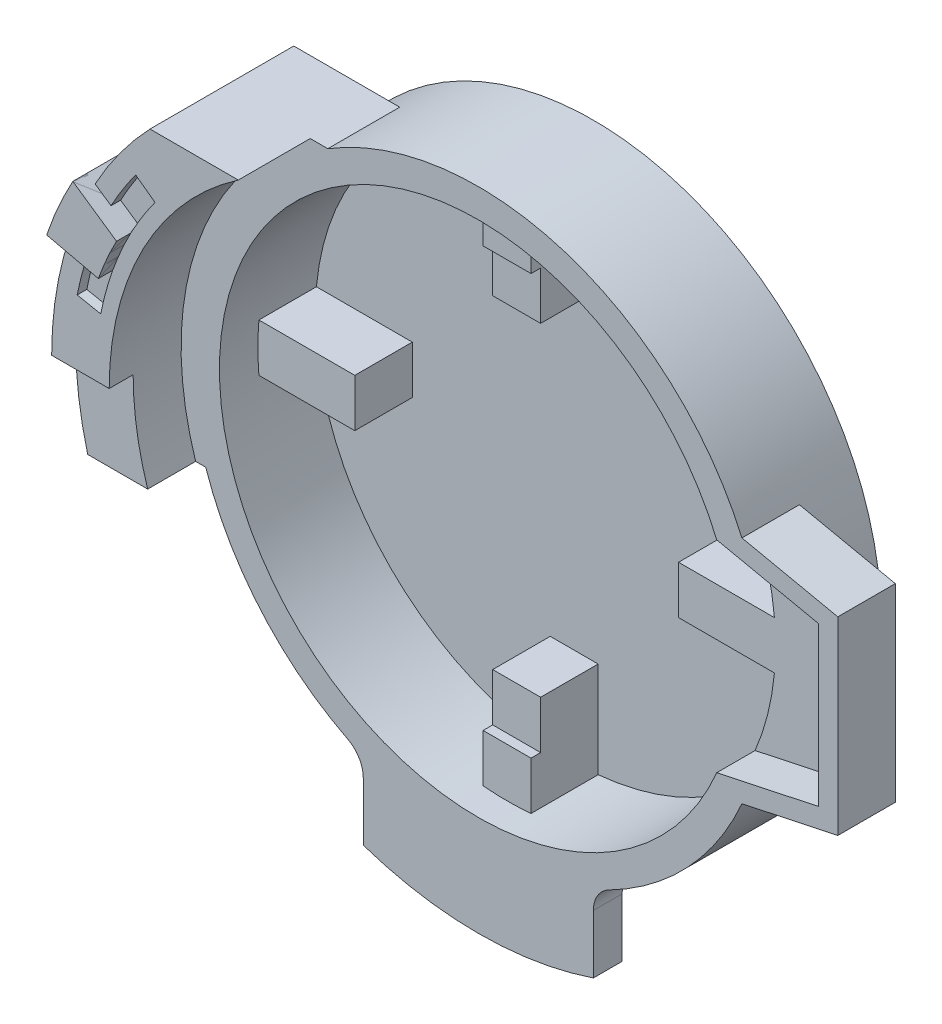
SolidWorks part; units mm, degrees
ref_plane "Front Plane" through (0, 0, 0) normal (0, 0, 1) x (1, 0, 0)
ref_plane "Top Plane" through (0, 0, 0) normal (0, 1, 0) x (1, 0, 0)
ref_plane "Right Plane" through (0, 0, 0) normal (1, 0, 0) x (0, 0, -1)
sketch "草图1" plane through (0, 0, 0) normal (0, 0, 1) x (1, 0, 0)
  circle A0 centre (0, 0) radius 30
  dimension "D1" = 60
extrude "凸台-拉伸1" add sketch "草图1" along normal blind 2
sketch "草图5" plane through (0, 0, 2) normal (0, 0, 1) x (1, 0, 0)
  circle A0 centre (0, 0) radius 30
  circle A1 centre (0, 0) radius 27
  dimension "D1" = 60
  dimension "D2" = 54
extrude "凸台-拉伸2" add sketch "草图5" along normal blind 10 contours A0 | A1
sketch "草图6" plane through (0, 0, 12) normal (0, 0, 1) x (1, 0, 0)
  line L0 (-12, -27.4955) -> (-12, -35.4955)
  line L2 (12, -35.4955) -> (12, -27.4955)
  circle A0 centre (0, 0) radius 30 construction
  arc A1 (-12, -27.4955) -> (12, -27.4955) centre (0, 0) ccw
  arc A2 (-12, -35.4955) -> (12, -35.4955) centre (0, 0) ccw
  dimension "D1" = 8
  dimension "D2" = 24
extrude "凸台-拉伸3" add sketch "草图6" against normal blind 3
fillet "圆角2" radius 3 1 edges at (-12, -27.4955, 10.5)
fillet "圆角3" radius 3 1 edges at (12, -27.4955, 10.5)
sketch "草图8" plane through (0, 0, 12) normal (0, 0, 1) x (1, 0, 0)
  line L0 (27.4945, -12.0022) -> (37.4945, -12.0022)
  line L1 (37.4945, -12.0022) -> (37.4945, 12.0022)
  line L2 (37.4945, 12.0022) -> (27.4945, 12.0022)
  circle A0 centre (0, 0) radius 30 construction
  arc A1 (27.4945, -12.0022) -> (27.4945, 12.0022) centre (0, 0) ccw
extrude "凸台-拉伸4" add sketch "草图8" against normal blind 6
sketch "草图13" plane through (0, 0, 12) normal (0, 0, 1) x (1, 0, 0)
  line L0 (-26.7466, 25.566) -> (-15.6965, 25.566)
  line L1 (-37, 0) -> (-30, 0)
  arc A0 (-26.7466, 25.566) -> (-37, 0) centre (0, 0) ccw
  arc A1 (-15.6965, 25.566) -> (-30, 0) centre (0, 0) ccw
  dimension "D1" = 37
  dimension "D2" = 30
extrude "凸台-拉伸6" add sketch "草图13" against normal mid plane 15
sketch "草图14" plane through (0, 0, 19.5) normal (0, 0, 1) x (1, 0, 0)
  circle A0 centre (0, 0) radius 31
  dimension "D1" = 62
extrude "切除-拉伸3" cut sketch "草图14" against normal up to surface (7.5 mm away) up to face at (6.7958, -12.5812, 12)
chamfer "倒角4" distance 10 angle 12 1 edges at (37.4945, 12.0022, 9) first distance on face at (32.4945, 12.0022, 9)
chamfer "倒角5" distance 10 angle 12 1 edges at (37.4945, -12.0022, 9) first distance on face at (32.4945, -12.0022, 9)
sketch "草图16" plane through (0, 0, 12) normal (0, 0, 1) x (1, 0, 0)
  line L0 (27.838, 9.8845) -> (35.4945, 8.257)
  line L1 (35.4945, 8.257) -> (35.4945, -8.257)
  line L2 (35.4945, -8.257) -> (21.8753, -11.1519)
  line L3 (21.8753, -11.1519) -> (18.3562, 11.8999)
  line L4 (18.3562, 11.8999) -> (27.838, 9.8845)
  line L5 (27.4945, -12.0022) -> (37.4945, -9.8766) construction
  line L6 (37.4945, -9.8766) -> (37.4945, 9.8766) construction
  line L7 (37.4945, 9.8766) -> (27.4945, 12.0022) construction
  line L8 (27.4945, -12.0022) -> (37.4945, -9.8766)
  line L9 (37.4945, -9.8766) -> (37.4945, 9.8766)
  line L10 (37.4945, 9.8766) -> (27.4945, 12.0022)
  circle M23 centre (0, 0) radius 27
  dimension "D1" = 2
  dimension "D2" = 2
  dimension "D3" = 2
extrude "切除-拉伸6" cut sketch "草图16" against normal blind 4 contours L4 L3 L2 M23 | L4 L2 L1 L0 M23 region at (30.7235, 0, 12) region at (23.1122, 1.1598, 12)
sketch "草图17" plane through (0, 0, 12) normal (0, 0, 1) x (1, 0, 0)
  line L0 (-28.4305, -9.5763) -> (-35.7393, -9.5763)
  line L1 (-37, 0) -> (-31, 0) construction
  line L2 (-30, 0) -> (-31, 0) construction
  line L3 (-37, 0) -> (-31, 0)
  line L4 (-30, 0) -> (-31, 0)
  arc A0 (-37, 0) -> (-35.7393, -9.5763) centre (0, 0) ccw
  arc A1 (-30, 0) -> (-28.4305, -9.5763) centre (0, 0) ccw
extrude "凸台-拉伸10" add sketch "草图17" along normal mid plane 10
sketch "草图18" plane through (0, 0, 12) normal (0, 0, 1) x (1, 0, 0)
  line L0 (-35.7393, -9.5763) -> (-28.4305, -9.5763) construction
  line L1 (-30, 0) -> (-31, 0) construction
  line L2 (-35.7393, -9.5763) -> (-28.4305, -9.5763)
  line L3 (-30, 0) -> (-31, 0)
  circle A0 centre (0, 0) radius 31
  circle A1 centre (0, 0) radius 30 construction
  circle A2 centre (0, 0) radius 30
  line M9 (-31, 0) -> (-30, 0)
  arc M10 (-30, 0) -> (-28.4305, -9.5763) centre (0, 0) ccw
extrude "切除-拉伸7" cut sketch "草图18" along normal blind 6 contours A0 L2 M9 M10 region at (-29.984, -4.8293, 12)
sketch "草图19" plane through (0, 0, 2) normal (0, 0, 1) x (1, 0, 0)
  line L0 (-2.5, 26.884) -> (-2.5, 16.884)
  line L1 (-2.5, 16.884) -> (2.5, 16.884)
  line L2 (2.5, 16.884) -> (2.5, 26.884)
  line L3 (26.884, 2.5) -> (16.884, 2.5)
  line L4 (16.884, -2.5) -> (26.884, -2.5)
  line L5 (16.884, 2.5) -> (16.884, -2.5)
  line L6 (2.5, -26.884) -> (2.5, -16.884)
  line L7 (-2.5, -16.884) -> (-2.5, -26.884)
  line L8 (2.5, -16.884) -> (-2.5, -16.884)
  line L9 (-26.884, -2.5) -> (-16.884, -2.5)
  line L10 (-16.884, 2.5) -> (-26.884, 2.5)
  line L11 (-16.884, -2.5) -> (-16.884, 2.5)
  circle A0 centre (0, 0) radius 27 construction
  arc A1 (24.868, 10.5158) -> (24.868, -10.5158) centre (0, 0) ccw construction
  arc A2 (2.5, 26.884) -> (-2.5, 26.884) centre (0, 0) ccw
  arc A3 (26.884, -2.5) -> (26.884, 2.5) centre (0, 0) ccw
  arc A4 (-2.5, -26.884) -> (2.5, -26.884) centre (0, 0) ccw
  arc A5 (-26.884, 2.5) -> (-26.884, -2.5) centre (0, 0) ccw
  point P26 (0, 0)
  dimension "D1" = 4
extrude "凸台-拉伸11" add sketch "草图19" along normal blind 6
sketch "草图20" plane through (0, 0, 8) normal (0, 0, 1) x (1, 0, 0)
  line L0 (-2.5, 26.884) -> (-2.5, 21.884)
  line L1 (-2.5, 21.884) -> (2.5, 21.884)
  line L2 (2.5, 21.884) -> (2.5, 26.884)
  line L9 (-2.5, 26.884) -> (-2.5, 16.884)
  line L10 (-2.5, 16.884) -> (2.5, 16.884)
  line L11 (2.5, 16.884) -> (2.5, 26.884)
  line L12 (-2.5, 26.884) -> (-2.5, 21.884)
  line L14 (2.5, 21.884) -> (2.5, 26.884)
  line L17 (2.5, -21.884) -> (2.5, -26.884)
  line L18 (-2.5, -26.884) -> (-2.5, -21.884)
  line L19 (2.5, -21.884) -> (2.5, -26.884)
  line L20 (-2.5, -21.884) -> (2.5, -21.884)
  line L21 (-2.5, -26.884) -> (-2.5, -21.884)
  arc A0 (2.5, -26.884) -> (-2.5, -26.884) centre (0, 0) cw
  arc A3 (2.5, 26.884) -> (-2.5, 26.884) centre (0, 0) ccw
  arc A4 (2.5, 26.884) -> (-2.5, 26.884) centre (0, 0) ccw
  arc M11 (2.5, 26.884) -> (-2.5, 26.884) centre (0, 0) ccw
  line M12 (-2.5, 26.884) -> (-2.5, 16.884)
  line M14 (2.5, 16.884) -> (2.5, 26.884)
  dimension "D1" = 0
extrude "凸台-拉伸12" add sketch "草图20" along normal blind 1 contours A0 L17 L20 L18 | L1 M12 M14 M11 region at (0, 24.4228, 8) region at (0, -24.4228, 8)
sketch "草图21" plane through (0, 0, 19.5) normal (0, 0, 1) x (1, 0, 0)
  line L2 (-28.7344, 15.1849) -> (-33.2959, 18.3135)
  line L3 (-30.6288, 10.8687) -> (-36.0194, 12.1079)
  arc A0 (-33.2959, 18.3135) -> (-36.0194, 12.1079) centre (0, 0) ccw
  arc A1 (-28.7344, 15.1849) -> (-30.6288, 10.8687) centre (0, 0) ccw
extrude "凸台-拉伸13" add sketch "草图21" along normal blind 1.5
sketch "草图26" plane through (0, 0, 21) normal (0, 0, 1) x (1, 0, 0)
  line L2 (-28.7344, 15.1849) -> (-33.2959, 18.3135)
  line L3 (-36.0194, 12.1079) -> (-30.6288, 10.8687)
  line L4 (-28.7344, 15.1849) -> (-33.2959, 18.3135)
  line L5 (-36.0194, 12.1079) -> (-30.6288, 10.8687)
  arc A2 (-28.7344, 15.1849) -> (-30.6288, 10.8687) centre (0, 0) ccw
  arc A3 (-33.2959, 18.3135) -> (-36.0194, 12.1079) centre (0, 0) ccw
  arc A4 (-28.7344, 15.1849) -> (-30.6288, 10.8687) centre (0, 0) ccw
  arc A5 (-33.2959, 18.3135) -> (-36.0194, 12.1079) centre (0, 0) ccw
  dimension "D1" = 0
extrude "凸台-拉伸14" add sketch "草图26" against normal up to surface (16.5 mm away) separate body contours A4 L5 A5 L4 up to face at (-28.8109, 13.4966, 4.5)
sketch "草图28" plane through (0, 0, 19.5) normal (0, 0, 1) x (1, 0, 0)
  line L1 (-26.2215, 19.2011) -> (-28.2386, 20.6781)
  line L2 (-31.8835, 6.3003) -> (-34.3361, 6.7849)
  line L3 (-35.04, 11.8827) -> (-30.6288, 10.8687) construction
  line L4 (-35.04, 11.8827) -> (-30.6288, 10.8687)
  line L5 (-28.7344, 15.1849) -> (-32.4671, 17.7451) construction
  line L6 (-28.7344, 15.1849) -> (-32.4671, 17.7451)
  arc A0 (-30.6288, 10.8687) -> (-31.8835, 6.3003) centre (0, 0) ccw
  arc A1 (-33.0803, 11.4322) -> (-34.3361, 6.7849) centre (0, 0) ccw
  arc A3 (-26.2215, 19.2011) -> (-28.7344, 15.1849) centre (0, 0) ccw
  arc A4 (-28.2386, 20.6781) -> (-30.8088, 16.6077) centre (0, 0) ccw
  line M5 (-30.6288, 10.8687) -> (-35.04, 11.8827)
extrude "切除-拉伸8" cut sketch "草图28" against normal blind 1 contours A1 L2 A0 M5 | L1 A4 L6 A3 region at (-28.5514, 17.9499, 19.5) region at (-32.5399, 8.8621, 19.5)
